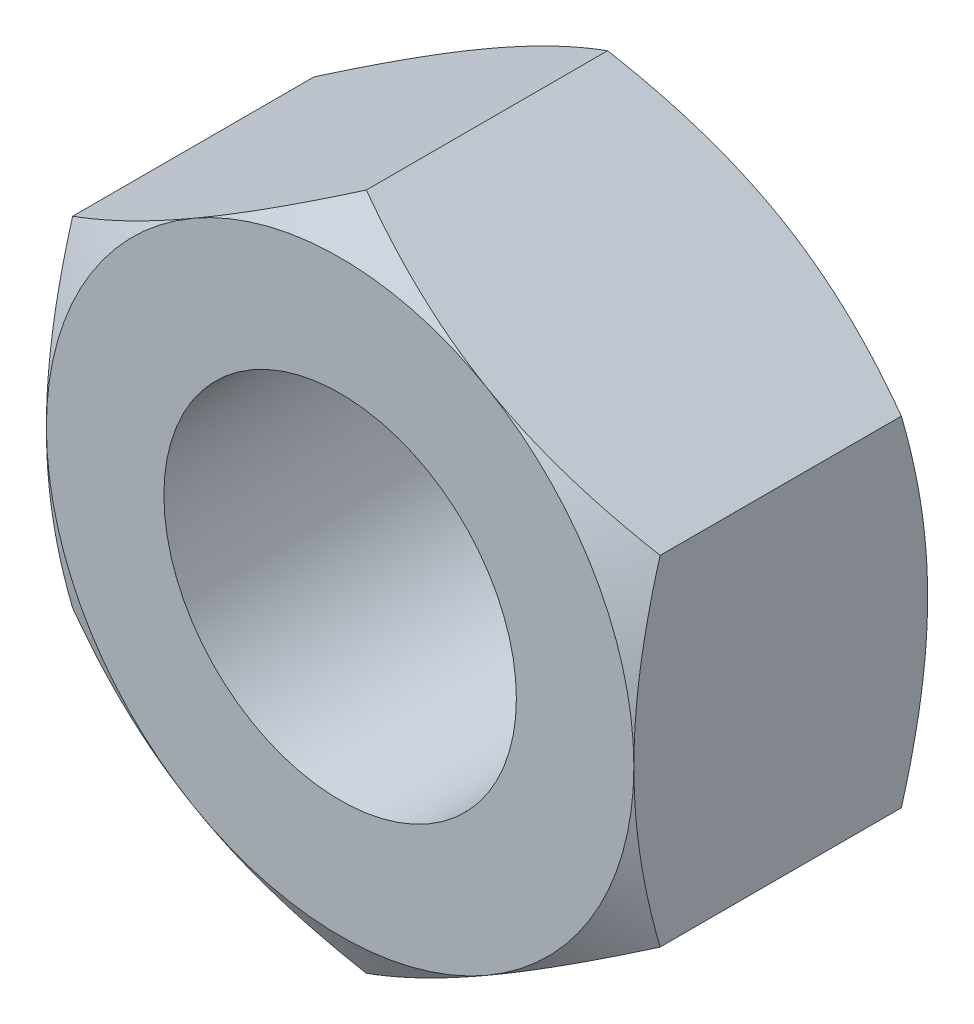
SolidWorks part; units mm, degrees
material "Plain Carbon Steel"
ref_plane "Front" through (0, 0, 0) normal (0, 0, 1) x (1, 0, 0)
ref_plane "Top" through (0, 0, 0) normal (0, 1, 0) x (1, 0, 0)
ref_plane "Right" through (0, 0, 0) normal (1, 0, 0) x (0, 0, -1)
sketch "Sketch1" plane through (0, 0, 0) normal (0, 0, 1) x (1, 0, 0)
  line L1 (-5, 2.8868) -> (-5, -2.8868)
  line L2 (-5, -2.8868) -> (0, -5.7735)
  line L3 (0, -5.7735) -> (5, -2.8868)
  line L4 (5, -2.8868) -> (5, 2.8868)
  line L5 (5, 2.8868) -> (0, 5.7735)
  line L6 (0, 5.7735) -> (-5, 2.8868)
  circle A0 centre (0, 0) radius 5 construction
  circle A1 centre (0, 0) radius 3 construction
  point P10 (0, 3)
  dimension "hex" = 10
  dimension "dia" = 6
extrude "Extrude1" add sketch "Sketch1" along normal mid plane 5
sketch "Sketch4" plane through (0, 0, -2.5) normal (0, 0, -1) x (-1, 0, 0)
  circle A0 centre (0, 0) radius 3 construction
  circle A1 centre (0, 0) radius 3
sketch "Sketch10" plane through (0, 0, 2.5) normal (0, 0, 1) x (1, 0, 0)
  circle A0 centre (0, 0) radius 3 construction
  circle A1 centre (0, 0) radius 3
extrude "Cut-Extrude2" cut sketch "Sketch10" against normal through all draft 45
sketch "Sketch11" plane through (0, 0, -2.5) normal (0, 0, -1) x (-1, 0, 0)
  circle A0 centre (0, 0) radius 3 construction
  circle A1 centre (0, 0) radius 3
extrude "Cut-Extrude3" cut sketch "Sketch11" against normal through all draft 45
sketch "Sketch13" plane through (0, 0, -2.5) normal (0, 0, -1) x (-1, 0, 0)
  circle A0 centre (0, 0) radius 3 construction
  circle A1 centre (0, 0) radius 3
extrude "Boss-Extrude1" add sketch "Sketch13" against normal up to vertex (5 mm away) separate body up to point (-5, 2.8868, 2.5)
curve "Helix/Spiral3" [suppressed] pitch 1 height 5 turns 5
sketch "Sketch12" plane through (0, 0, 0) normal (1, 0, 0) x (0, 0, -1)
  line L0 (3.375, 3) -> (2.5, 3)
  line L1 (3.375, 3) -> (3, 2.3505)
  line L2 (3, 2.3505) -> (2.875, 2.3505)
  line L3 (2.875, 2.3505) -> (2.5, 3)
  line L4 (2.9375, 2.3505) -> (2.9375, 3) construction
  line L5 (2.6875, 2.6752) -> (3.1875, 2.6752) construction
  dimension "D1" = 60
  dimension "D2" = 0.125
  dimension "D3" = 0.5
sweep "Cut-Sweep1" [suppressed] cut profiles "Sketch12" path "Helix/Spiral3"
combine bodies "Combine1" operation type subtract main body 116 bodies to subtract 117
sketch "Sketch7" plane through (0, 0, 2.5) normal (0, 0, 1) x (1, 0, 0)
  circle A0 centre (0, 0) radius 5 construction
  circle A1 centre (0, 0) radius 5
extrude "Extrude2" cut sketch "Sketch7" against normal blind 25.4 draft 60 flip side to cut
mirror "Mirror2" about plane through (0, 0, 0) normal (0, 0, 1) of "Extrude2"
sketch "Sketch8" plane through (0, 0, 2.5) normal (0, 0, 1) x (1, 0, 0)
  line L0 (-2.1213, 2.1213) -> (0, 0) construction
  line L1 (0, -2.9882) -> (0, 2.9882) construction
  circle A1 centre (0, 0) radius 3 construction
  point P0 (-2.1213, 2.1213)
  dimension "D1" = 45
sketch "Sketch14" plane through (0, 0, 2.5) normal (0, 0, 1) x (1, 0, 0)
  line L0 (0, 0) -> (-3, 0) construction
  circle A0 centre (0, 0) radius 3 construction
equation "\"D3@Helix/Spiral3\" = \"length@Extrude1\" "
equation "\"D2@Sketch12\" = \"D4@Helix/Spiral3\"*.125"
equation "\"D3@Sketch12\" = \"D4@Helix/Spiral3\"*.50"
